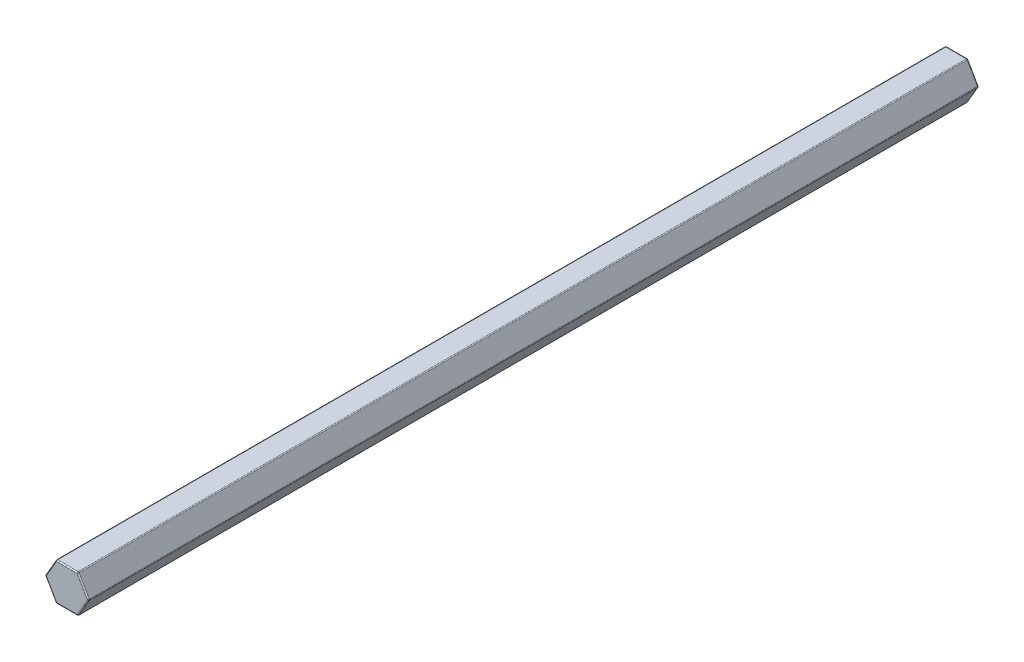
SolidWorks part; units mm, degrees
ref_plane "Front Plane" through (0, 0, 0) normal (0, 0, 1) x (1, 0, 0)
ref_plane "Top Plane" through (0, 0, 0) normal (0, 1, 0) x (1, 0, 0)
ref_plane "Right Plane" through (0, 0, 0) normal (1, 0, 0) x (0, 0, -1)
sketch "Sketch1" plane through (0, 0, 0) normal (0, 0, 1) x (1, 0, 0)
  line L1 (3.6662, 0) -> (1.8331, 3.175)
  line L2 (1.8331, 3.175) -> (-1.8331, 3.175)
  line L3 (-1.8331, 3.175) -> (-3.6662, 0)
  line L4 (-3.6662, 0) -> (-1.8331, -3.175)
  line L5 (-1.8331, -3.175) -> (1.8331, -3.175)
  line L6 (1.8331, -3.175) -> (3.6662, 0)
  circle A0 centre (0, 0) radius 3.175 construction
  dimension "D1" = 6.35
extrude "Boss-Extrude1" add sketch "Sketch1" along normal mid plane 150
fillet "Fillet1" radius 0.2 18 edges at (2.7496, 1.5875, -75) (-2.7496, 1.5875, -75) (0, -3.175, -75) (-3.6662, 0, 0) (-1.8331, -3.175, 0) (-2.7496, -1.5875, -75) (1.8331, -3.175, 0) (3.6662, 0, 0) (2.7496, -1.5875, -75) (1.8331, 3.175, 0) (-1.8331, 3.175, 0) (0, 3.175, -75) (0, -3.175, 75) (-2.7496, -1.5875, 75) (-2.7496, 1.5875, 75) (0, 3.175, 75) (2.7496, 1.5875, 75) (2.7496, -1.5875, 75)
ref_axis "Axis1" through (0, 0, -165) along (0, 0, 1)
